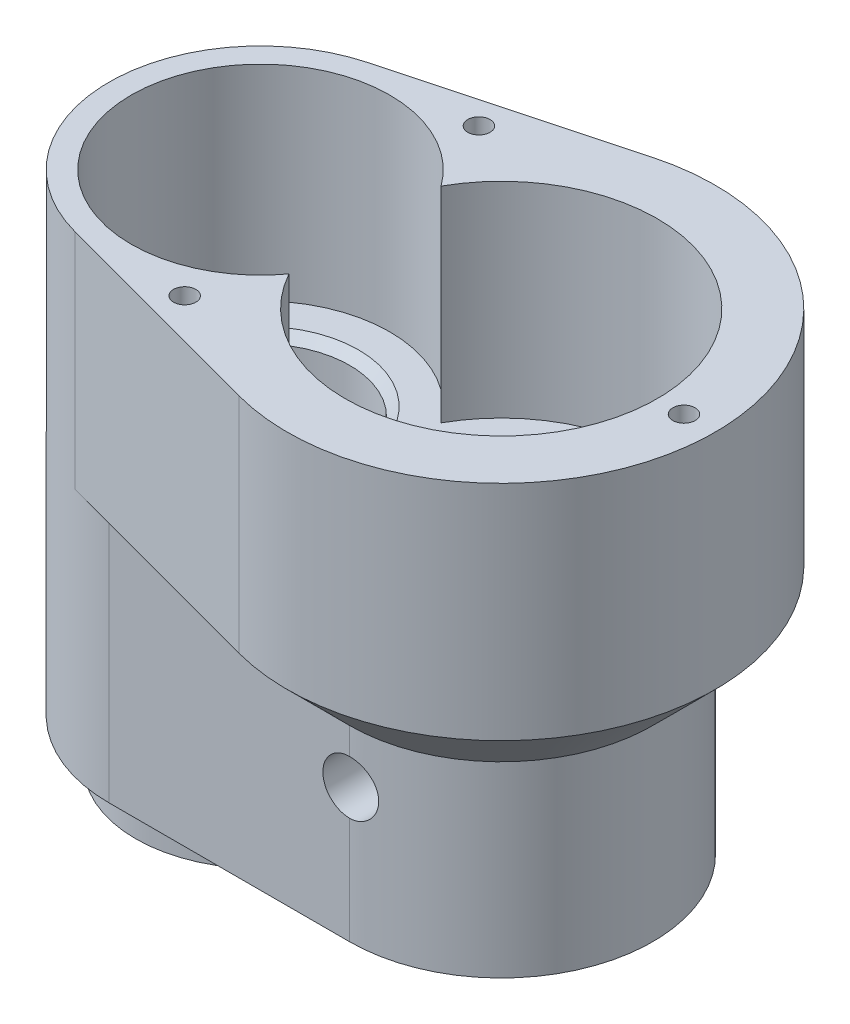
SolidWorks part; units mm, degrees
ref_plane "前视基准面" through (0, 0, 0) normal (0, 0, 1) x (1, 0, 0)
ref_plane "上视基准面" through (0, 0, 0) normal (0, 1, 0) x (1, 0, 0)
ref_plane "右视基准面" through (0, 0, 0) normal (1, 0, 0) x (0, 0, -1)
sketch "草图1" plane through (0, 0, 0) normal (0, 1, 0) x (1, 0, 0)
  circle A0 centre (0, 0) radius 14
  dimension "D1" = 28
extrude "凸台-拉伸1" add sketch "草图1" along normal blind 5
sketch "草图2" plane through (0, 5, 0) normal (0, 1, 0) x (1, 0, 0)
  line L0 (0, 0) -> (27, 0) construction
  line L1 (0, 17) -> (27, 17)
  line L2 (0, -17) -> (27, -17)
  arc A0 (0, 17) -> (0, -17) centre (0, 0) ccw
  arc A1 (27, -17) -> (27, 17) centre (27, 0) ccw
  point P3 (13.5, 0)
  dimension "D1" = 17
  dimension "D2" = 27
extrude "凸台-拉伸2" add sketch "草图2" along normal blind 53
sketch "草图3" plane through (0, 58, 0) normal (0, 1, 0) x (1, 0, 0)
  line L0 (20.7778, 23.1794) -> (-4.4074, 16.4187)
  line L1 (20.7778, -23.1794) -> (-4.4074, -16.4187)
  circle A0 centre (27, 0) radius 24
  arc A1 (0, 17) -> (0, -17) centre (0, 0) ccw construction
  arc A2 (0, 17) -> (0, -17) centre (0, 0) ccw
  arc M2 (0, 17) -> (0, -17) centre (0, 0) ccw
  line M3 (0, -17) -> (27, -17)
  arc M4 (27, -17) -> (27, 17) centre (27, 0) ccw
  line M5 (27, 17) -> (0, 17)
  dimension "D1" = 48
extrude "凸台-拉伸3" add sketch "草图3" against normal offset from surface (32 mm away) 21 contours A0 M5 M4 M3 | A0 L0 M2 M5 | A0 L1 M3 M2 region at (8.2306, 58, -18.7654) region at (41.222, 58, -18.5432) region at (8.2306, 58, 18.7654) up to face at (0, 5, 14)
chamfer "倒角1" distance 7 angle 45 3 edges at (8.1852, 26, -19.7991) (8.1852, 26, 19.7991) (51, 26, 0)
sketch "草图4" plane through (0, 58, 0) normal (0, 1, 0) x (1, 0, 0)
  arc A0 (11.7222, 8.5346) -> (11.7222, -8.5346) centre (0, 0) ccw
  arc A1 (11.7222, -8.5346) -> (11.7222, 8.5346) centre (27, 0) ccw
  dimension "D1" = 29
  dimension "D2" = 35
extrude "切除-拉伸1" cut sketch "草图4" against normal blind 23
sketch "草图6" plane through (0, 35, 0) normal (0, 1, 0) x (1, 0, 0)
  circle A0 centre (0, 0) radius 10
  circle A1 centre (27, 0) radius 8
  dimension "D1" = 20
  dimension "D2" = 16
extrude "切除-拉伸2" cut sketch "草图6" against normal through all
chamfer "倒角2" distance 1 angle 45 4 edges at (0, 35, 10) (0, 0, 10) (27, 5, 8) (27, 35, 8)
sketch "草图7" plane through (0, 58, 0) normal (0, 1, 0) x (1, 0, 0)
  line L0 (-31.9, 0) -> (31.9, 0) construction
  line L1 (0, 0) -> (11.495, 0) construction
  line L2 (0, -26.4) -> (0, 26.4) construction
  arc A0 (11.7222, -8.5346) -> (11.7222, 8.5346) centre (27, 0) ccw construction
  point P0 (47.5, 0)
  point P1 (8, 16.5)
  point P7 (8, -16.5)
  dimension "D1" = 33
  dimension "D2" = 20.5
  dimension "D3" = 8
hole_wizard "M3 螺纹孔1" positions "草图7" profile "草图8" tap size "M3" standard "GB"
sketch "草图8" plane through (47.5, 58, 0) normal (1, 0, 0) x (0, 0, 1)
  line L0 (0, 0) -> (0, 8.7511)
  line L1 (0, 8.7511) -> (1.25, 8)
  line L2 (1.25, 8) -> (1.25, 0)
  line L5 (1.25, 0) -> (0, 0)
  line L10 (0, 8.7511) -> (-1.25, 8) construction
  line L11 (0, -6.35) -> (0, 107.95) construction
  dimension "螺纹孔钻头直径" = 2.5
  dimension "螺纹孔钻头深度" = 8
  dimension "导头角度" = 118
cosmetic thread "孔螺纹线1" parameters "D1"=6, "D2"=3
cosmetic thread "孔螺纹线2" parameters "D1"=6, "D2"=3
cosmetic thread "孔螺纹线3" parameters "D1"=6, "D2"=3
sketch "草图9" plane through (0, 0, 17) normal (0, 0, 1) x (1, 0, 0)
  line L0 (27, 26) -> (27, 5) construction
  line L1 (27, 5) -> (44, 5) construction
  circle A0 centre (27, 20) radius 3
  dimension "D1" = 6
  dimension "D2" = 15
extrude "切除-拉伸3" cut sketch "草图9" against normal through all
